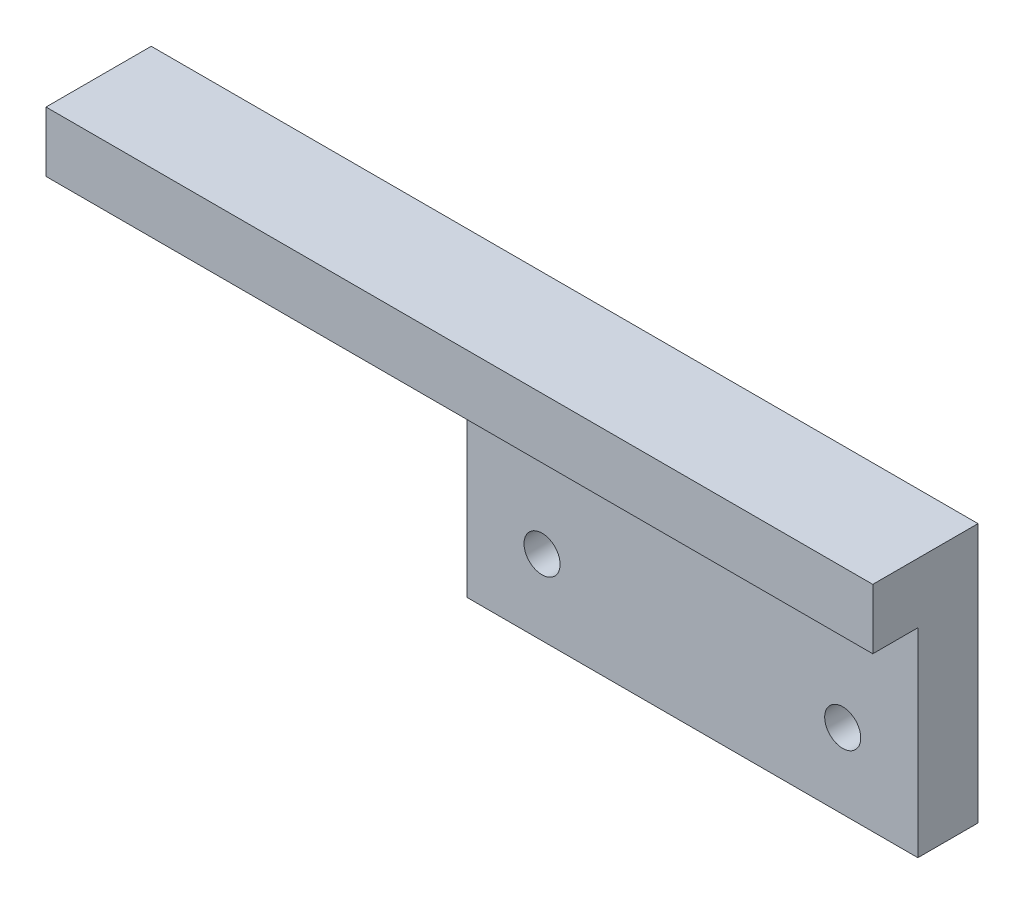
SolidWorks part; units mm, degrees
ref_plane "정면" through (0, 0, 0) normal (0, 0, 1) x (1, 0, 0)
ref_plane "윗면" through (0, 0, 0) normal (0, 1, 0) x (1, 0, 0)
ref_plane "우측면" through (0, 0, 0) normal (1, 0, 0) x (0, 0, -1)
sketch "스케치1" plane through (0, 0, 0) normal (0, 0, 1) x (1, 0, 0)
  line L1 (-30, 13.25) -> (30, 13.25)
  line L2 (-30, 13.25) -> (-30, -13.25)
  line L3 (-30, -13.25) -> (30, -13.25)
  line L4 (30, 13.25) -> (30, -13.25)
  line L5 (-30, 13.25) -> (30, -13.25) construction
  line L6 (-30, -13.25) -> (30, 13.25) construction
  point P0 (0, 0)
  dimension "D1" = 26.5
  dimension "D2" = 60
extrude "보스-돌출1" add sketch "스케치1" along normal blind 8
sketch "스케치2" plane through (0, 0, 8) normal (0, 0, 1) x (1, 0, 0)
  line L0 (30, -13.25) -> (30, 13.25) construction
  line L1 (-30, 13.25) -> (30, 13.25)
  line L2 (-30, 13.25) -> (-30, 21.25)
  line L3 (-30, 21.25) -> (30, 21.25)
  line L4 (30, 13.25) -> (30, 21.25)
  dimension "D1" = 8
extrude "보스-돌출2" add sketch "스케치2" against normal up to vertex (8 mm away) and the other way blind 6 up to point (30, 13.25, 0)
hole_wizard "M4 소켓 머리 캡 나사용 카운터보어1" positions "스케치5" profile "스케치6" counterbore size "M4" standard "KS"
sketch "스케치5" plane through (0, 0, 0) normal (0, 0, -1) x (-1, 0, 0)
  line L0 (30, -13.25) -> (-30, -13.25) construction
  line L1 (30, 21.25) -> (30, -13.25) construction
  line L2 (-30, -13.25) -> (-30, 21.25) construction
  point P0 (-20, -3.25)
  point P2 (20, -3.25)
  dimension "D1" = 10
  dimension "D2" = 10
  dimension "D3" = 10
  dimension "D4" = 10
sketch "스케치6" plane through (20, -3.25, 0) normal (1, 0, 0) x (0, 1, 0)
  line L0 (0, 0) -> (0, 11.5421)
  line L1 (0, 11.5421) -> (2.4, 10.1)
  line L2 (2.4, 10.1) -> (2.4, 4)
  line L3 (2.4, 4) -> (4, 4)
  line L4 (4, 4) -> (4, 0)
  line L5 (4, 0) -> (0, 0)
  line L10 (0, 11.5421) -> (-2.4, 10.1) construction
  line L11 (0, -6.35) -> (0, 107.95) construction
  dimension "구멍 지름" = 4.8
  dimension "구멍 깊이" = 10.1
  dimension "카운터보어 지름" = 8
  dimension "카운터보어 깊이" = 4
  dimension "드릴 각도" = 118
sketch "스케치7" plane through (-30, 0, 0) normal (-1, 0, 0) x (0, 0, 1)
  line L1 (0, 21.25) -> (14, 21.25)
  line L2 (0, 21.25) -> (0, 13.25)
  line L3 (0, 13.25) -> (14, 13.25)
  line L4 (14, 21.25) -> (14, 13.25)
extrude "보스-돌출3" add sketch "스케치7" along normal blind 50
